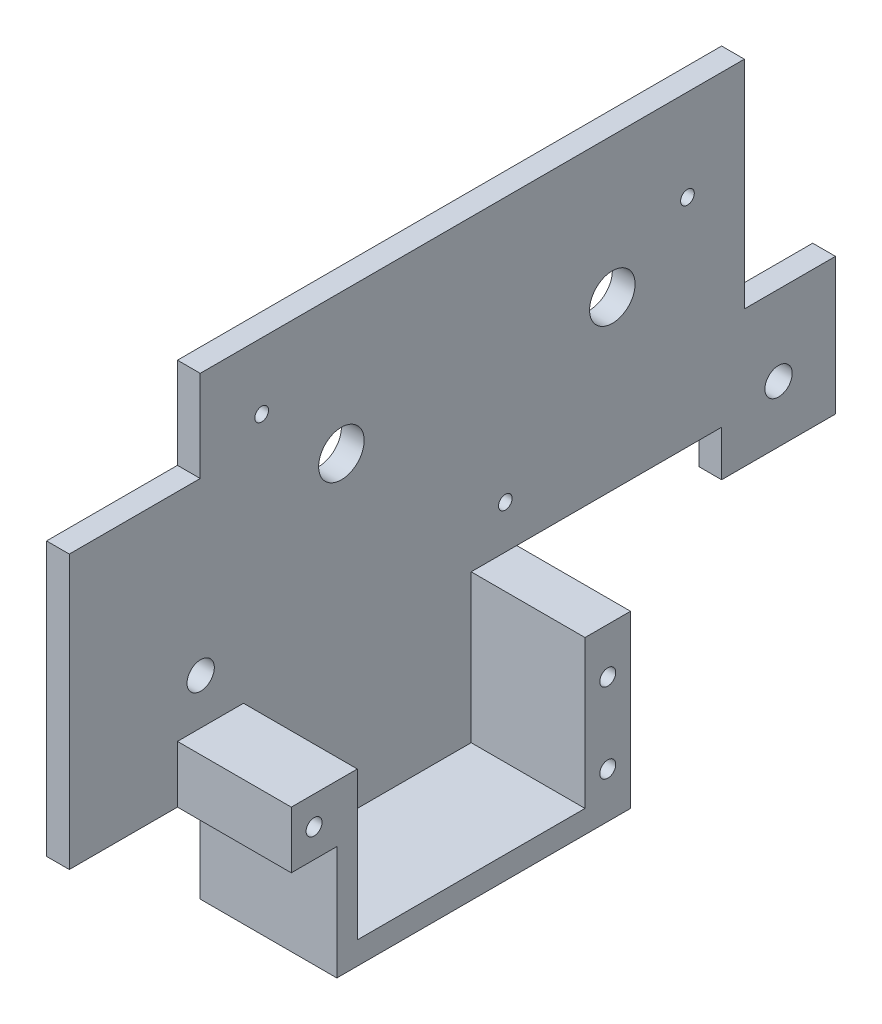
SolidWorks part; units mm, degrees
ref_plane "前视基准面" through (0, 0, 0) normal (0, 0, 1) x (1, 0, 0)
ref_plane "上视基准面" through (0, 0, 0) normal (0, 1, 0) x (1, 0, 0)
ref_plane "右视基准面" through (0, 0, 0) normal (1, 0, 0) x (0, 0, -1)
other "Configuration Table"
sketch "草图1" plane through (0, 0, 0) normal (1, 0, 0) x (0, 0, -1)
  line L5 (0, 0) -> (-28, 0)
  line L6 (0, 0) -> (0, -13.5)
  line L7 (0, -13.5) -> (-28, -13.5)
  line L8 (-28, 0) -> (-28, -13.5)
  dimension "D1" = 28
  dimension "D2" = 13.5
extrude "凸台-拉伸1" add sketch "草图1" along normal blind 1 contours L7 L8 L5 L6 | L8 L7 L6 L5 region at (0, -6.75, 14)
sketch "草图2" plane through (1, 0, 0) normal (1, 0, 0) x (0, 0, -1)
  line L0 (0, 0) -> (0, -13.5) construction
  line L1 (0, 0) -> (-28, 0) construction
  line L2 (0, -13.5) -> (-28, -13.5) construction
  line L3 (0, -10.5) -> (5, -10.5)
  line L4 (0, -10.5) -> (0, -15.5)
  line L5 (0, -15.5) -> (5, -15.5)
  line L6 (5, -10.5) -> (5, -15.5)
  line L7 (-28, 0) -> (-28, -13.5) construction
  line L8 (-28, -9.5) -> (-10, -9.5)
  line L9 (-28, -9.5) -> (-28, -13.5)
  line L10 (-28, -13.5) -> (-10, -13.5)
  line L11 (-10, -9.5) -> (-10, -13.5)
  line L13 (0, -9.5) -> (5, -9.5)
  line L14 (0, -9.5) -> (0, -10.5)
  line L15 (0, -10.5) -> (5, -10.5)
  line L16 (5, -9.5) -> (5, -10.5)
  circle A0 centre (-1.5, -4) radius 0.3
  circle A2 centre (-20.2, -2.9) radius 0.3
  circle A3 centre (-9.5, -11.6) radius 0.3
  circle A5 centre (2.5, -13) radius 0.6
  point P27 (2.5, -10.5)
  point P29 (5, -13)
  line M4 (-28, -13.5) -> (0, -13.5)
  line M5 (0, -13.5) -> (0, 0)
  dimension "D2" = 0.6
  dimension "D11" = 18.7
  dimension "D9" = 1.2
  dimension "D1" = 1.5
  dimension "D3" = 4
  dimension "D4" = 5
  dimension "D5" = 3
  dimension "D6" = 5
  dimension "D7" = 4
  dimension "D8" = 18
  dimension "D10" = 8
  dimension "D12" = 1
  dimension "D13" = 1.1
  dimension "D14" = 7.6
extrude "切除-拉伸1" cut sketch "草图2" against normal through all contours A0 | A3 | A2
extrude "凸台-拉伸2" add sketch "草图2<3>" against normal up to surface (1 mm away) contours L16 L13 L3 M5 | L4 M4 | L4 L5 L6 L3 region at (1, -10, -2.5) up to face at (0, -4, 1.2)
sketch "草图2<3>" plane through (1, 0, 0) normal (1, 0, 0) x (0, 0, -1) same geometry as "草图2"
extrude "切除-拉伸2" cut sketch "草图2<4>" against normal through all contours A5
sketch "草图2<4>" plane through (1, 0, 0) normal (1, 0, 0) x (0, 0, -1) same geometry as "草图2"
sketch "草图3" plane through (1, 0, 0) normal (1, 0, 0) x (0, 0, -1)
  line L2 (0, 0) -> (-28, 0) construction
  circle A0 centre (-4.8, -6.15) radius 1
  circle A1 centre (-16.7, -6.15) radius 1
  circle A2 centre (-1.5, -4) radius 0.3 construction
  dimension "D1" = 2
  dimension "D2" = 2
  dimension "D3" = 11.9
  dimension "D4" = 3.3
  dimension "D5" = 6.15
extrude "切除-拉伸3" cut sketch "草图3" against normal through all contours A1 | A0
sketch "草图4" plane through (1, 0, 0) normal (1, 0, 0) x (0, 0, -1)
  line L0 (0, 0) -> (-28, 0) construction
  line L1 (-22.9, 0) -> (-29.9, 0)
  line L2 (-22.9, 0) -> (-22.9, -4)
  line L3 (-22.9, -4) -> (-29.9, -4)
  line L4 (-29.9, 0) -> (-29.9, -4)
  dimension "D2" = 7
  dimension "D3" = 4
extrude "切除-拉伸4" cut sketch "草图4" against normal blind 1.5
sketch "草图5" plane through (0, 0, 0) normal (-1, 0, 0) x (0, 0, 1)
  circle A0 centre (22.8807, -11.5) radius 0.6
  dimension "D1" = 1.2
extrude "切除-拉伸5" cut sketch "草图5" against normal through all
sketch "草图6" plane through (1, 0, 0) normal (1, 0, 0) x (0, 0, -1)
  line L0 (0, -9.5) -> (5, -9.5) construction
  line L1 (0, 0) -> (1, 0)
  line L2 (0, 0) -> (0, -9.5)
  line L3 (0, -9.5) -> (1, -9.5)
  line L4 (1, 0) -> (1, -9.5)
  dimension "D1" = 1
extrude "凸台-拉伸3" add sketch "草图6" against normal up to surface (1 mm away) contours L4 L3 L2 L1 up to face at (0, -11.5, 23.4807)
sketch "草图7" plane through (1, 0, 0) normal (1, 0, 0) x (0, 0, -1)
  line L0 (1, 0) -> (-22.9, 0) construction
  line L1 (-11, -10) -> (-21, -10)
  line L2 (-11, -10) -> (-11, -20)
  line L3 (-11, -20) -> (-21, -20)
  line L4 (-21, -10) -> (-21, -20)
  line L15 (0, -13.5) -> (-28, -13.5) construction
  line L20 (-11, -13.5) -> (-9, -13.5)
  line L21 (-11, -13.5) -> (-11, -20)
  line L26 (-11, -20) -> (-9, -20)
  line L27 (-9, -13.5) -> (-9, -20)
  line L33 (-21, -20) -> (-9, -20)
  line L34 (-21, -20) -> (-21, -21)
  line L35 (-21, -21) -> (-9, -21)
  line L36 (-9, -20) -> (-9, -21)
  line L37 (-21, -21) -> (-21.9, -21)
  line L38 (-21, -21) -> (-21, -13.5)
  line L39 (-21, -13.5) -> (-21.9, -13.5)
  line L40 (-21.9, -21) -> (-21.9, -13.5)
  line L41 (-21.9, -13.5) -> (-23.9, -13.5)
  line L42 (-21.9, -13.5) -> (-21.9, -16)
  line L43 (-21.9, -16) -> (-23.9, -16)
  line L44 (-23.9, -13.5) -> (-23.9, -16)
  circle A0 centre (-10, -19) radius 0.35
  circle A1 centre (-10, -15.5) radius 0.35
  circle A2 centre (-22.9, -14.75) radius 0.35
  point P26 (-23.9, -14.75)
  point P27 (-22.9, -16)
  point P28 (-10, -13.5)
  line M7 (-28, -13.5) -> (0, -13.5)
  dimension "D9" = 0.7
  dimension "D1" = 10
  dimension "D2" = 10
  dimension "D3" = 11
  dimension "D4" = 2
  dimension "D5" = 1
  dimension "D6" = 0.9
  dimension "D7" = 2.5
  dimension "D8" = 2
  dimension "D10" = 2
  dimension "D11" = 2
extrude "凸台-拉伸4" add sketch "草图7" against normal up to surface (1 mm away) contours L44 L43 L40 M7 | L40 L37 L34 L4 M7 | L4 L3 L2 M7 | L36 L26 L3 L34 L35 | L27 L2 L26 M7 region at (1, -16.7185, 10) region at (1, -16.75, 16) region at (1, -17.25, 21.45) region at (1, -20.5, 15) region at (1, -14.75, 21.932) up to face at (0, -11.5, 23.4807)
extrude "凸台-拉伸5" add sketch "草图7<3>" along normal blind 5 from surface contours L40 L37 L34 L4 M7 | L44 L43 L40 A2 M7 | L36 L26 L3 L34 L35 | L27 L2 L26 A1 A0 M7 region at (1, -16.7185, 10) region at (1, -17.25, 21.45) region at (1, -20.5, 15) region at (1, -14.75, 21.932) starting at face at (1, -11.5, 23.4807)
sketch "草图7<3>" plane through (1, 0, 0) normal (1, 0, 0) x (0, 0, -1) same geometry as "草图7"
sketch "草图8" plane through (1, 0, 0) normal (1, 0, 0) x (0, 0, -1)
  line L7 (-23.9, -16) -> (-28.65, -16)
  line L8 (-23.9, -16) -> (-23.9, -13.5)
  line L9 (-23.9, -13.5) -> (-28.65, -13.5)
  line L10 (-28.65, -16) -> (-28.65, -13.5)
  line L11 (-28, -4) -> (-28.65, -4)
  line L12 (-28, -4) -> (-28, -13.5)
  line L13 (-28, -13.5) -> (-28.65, -13.5)
  line L14 (-28.65, -4) -> (-28.65, -13.5)
  line M15 (-28, -4) -> (-28, -13.5)
  line M16 (-28, -13.5) -> (-23.9, -13.5)
  dimension "D1" = 0.65
extrude "凸台-拉伸6" add sketch "草图8" against normal up to surface (1 mm away) contours L11 L14 L9 M15 | L10 L7 L8 L9 M16 region at (1, -14.75, 26.275) region at (1, -8.75, 28.325) up to face at (0, -11.5, 23.4807)
